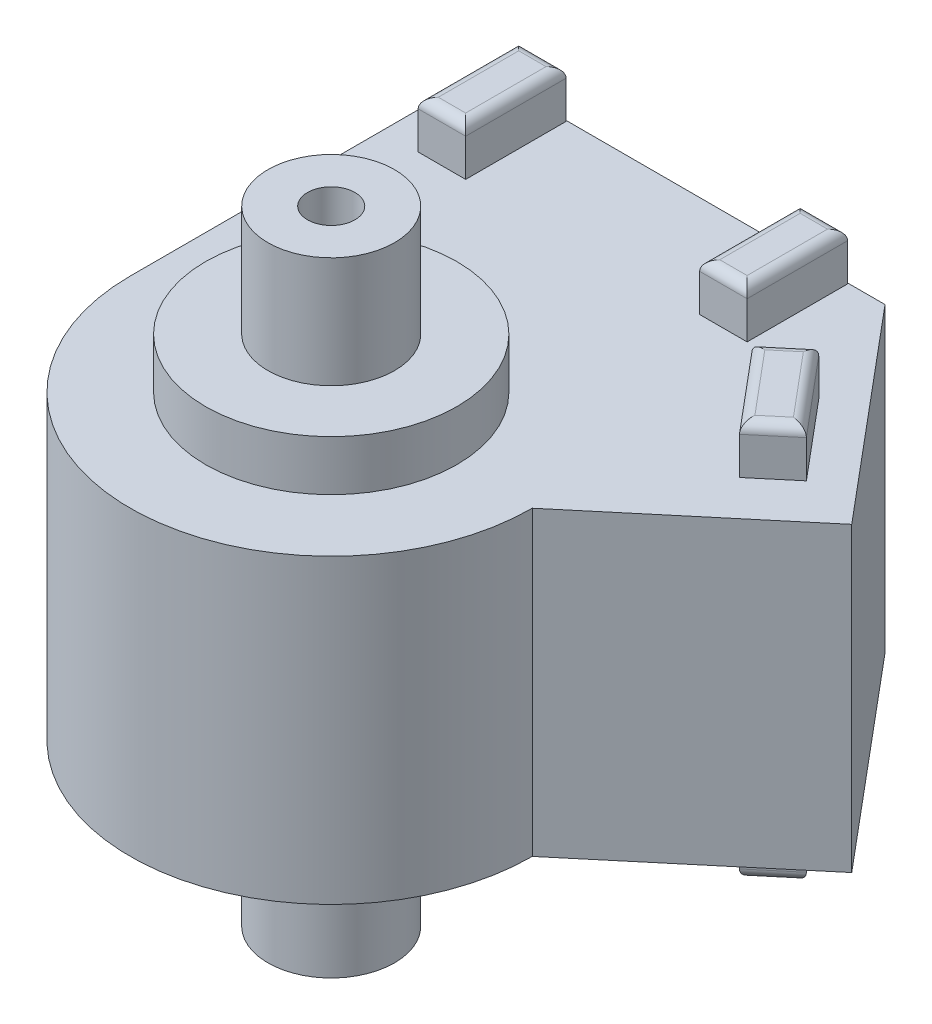
SolidWorks part; units mm, degrees
ref_plane "Front Plane" through (0, 0, 0) normal (0, 0, 1) x (1, 0, 0)
ref_plane "Top Plane" through (0, 0, 0) normal (0, 1, 0) x (1, 0, 0)
ref_plane "Right Plane" through (0, 0, 0) normal (1, 0, 0) x (0, 0, -1)
sketch "Sketch1" plane through (0, 0, 0) normal (0, 0, 1) x (1, 0, 0)
  line L0 (-12.7, -9.525) -> (-12.7, 9.525)
  line L1 (-12.7, 9.525) -> (-7.9375, 9.525)
  line L2 (-7.9375, 9.525) -> (-7.9375, 12.7)
  line L3 (-7.9375, 12.7) -> (-4, 12.7)
  line L4 (-4, 12.7) -> (-4, 19.7)
  line L5 (0, 0) -> (0, 19.7) construction
  line L6 (0, 19.7) -> (-4, 19.7)
  line L7 (0, 0) -> (-12.7, 0) construction
  line L8 (-4, 19.7) -> (4, 19.7) construction
  line L9 (-7.9375, 12.7) -> (7.9375, 12.7) construction
  line L10 (-12.7, 9.525) -> (12.7, 9.525) construction
  line L11 (-12.7, -9.525) -> (-7.9375, -9.525)
  line L12 (-7.9375, -9.525) -> (-7.9375, -12.7)
  line L13 (-7.9375, -12.7) -> (-4, -12.7)
  line L14 (-4, -12.7) -> (-4, -19.7)
  line L15 (-4, -19.7) -> (0, -19.7)
  line L16 (0, -19.7) -> (0, 19.7)
  point P9 (0, 9.525)
  point P12 (0, 19.7)
  point P14 (0, 12.7)
  dimension "D1" = 19.05
  dimension "D2" = 3.175
  dimension "D3" = 7
  dimension "D4" = 8
  dimension "D5" = 15.875
  dimension "D6" = 25.4
  dimension "D7" = 25.4
revolve "Revolve1" add sketch "Sketch1" angle 360 about L5 region at (-5.3061, 0, 0)
sketch "Sketch2" plane through (0, 9.525, 0) normal (0, 1, 0) x (1, 0, 0)
  line L0 (12.7, 0) -> (23.6726, 9.2071)
  line L1 (23.6726, 9.2071) -> (12.7, 22.2837)
  line L3 (12.7, 22.2837) -> (-12.7, 22.2837)
  line L4 (-12.7, 22.2837) -> (-12.7, 0)
  line L5 (-12.7, 0) -> (12.7, 0)
  line L6 (12.7, 0) -> (12.7, 22.2837) construction
  circle A0 centre (0, 0) radius 12.7 construction
  dimension "D1" = 50
  dimension "D2" = 25.4
extrude "Boss-Extrude1" add sketch "Sketch2" against normal up to surface (19.05 mm away) up to face at (7.9375, -9.525, 0)
sketch "Sketch3" plane through (0, 19.7, 0) normal (0, 1, 0) x (1, 0, 0)
  circle A0 centre (0, 0) radius 1.4986
  dimension "D1" = 2.9972
extrude "Cut-Extrude1" cut sketch "Sketch3" against normal through all
sketch "Sketch4" plane through (0, 9.525, 0) normal (0, 1, 0) x (1, 0, 0)
  line L5 (15.7794, 15.0179) -> (13.4834, 13.0913)
  line L6 (13.4834, 13.0913) -> (17.5651, 8.227)
  line L7 (17.5651, 8.227) -> (19.8611, 10.1535)
  line L8 (19.8611, 10.1535) -> (15.7794, 15.0179)
  line L9 (12.7, 0) -> (23.6726, 9.2071) construction
  line L10 (23.6726, 9.2071) -> (12.7, 22.2837) construction
  dimension "D1" = 2.9972
  dimension "D2" = 6.35
  dimension "D3" = 3.175
  dimension "D4" = 2.3114
extrude "Boss-Extrude2" add sketch "Sketch4" along normal blind 2.9972
sketch "Sketch5" plane through (0, 9.525, 0) normal (0, 1, 0) x (1, 0, 0)
  line L0 (-12.7, 22.2837) -> (-12.7, 0) construction
  line L1 (-10.3886, 22.2329) -> (-7.3914, 22.2329)
  line L2 (-10.3886, 22.2329) -> (-10.3886, 15.8829)
  line L3 (-10.3886, 15.8829) -> (-7.3914, 15.8829)
  line L4 (-7.3914, 22.2329) -> (-7.3914, 15.8829)
  line L5 (-10.3886, 22.2329) -> (-7.3914, 15.8829) construction
  line L6 (-10.3886, 15.8829) -> (-7.3914, 22.2329) construction
  line L7 (7.3914, 22.2329) -> (10.3886, 22.2329)
  line L8 (7.3914, 22.2329) -> (7.3914, 15.8829)
  line L9 (7.3914, 15.8829) -> (10.3886, 15.8829)
  line L10 (10.3886, 22.2329) -> (10.3886, 15.8829)
  line L11 (7.3914, 22.2329) -> (10.3886, 15.8829) construction
  line L12 (7.3914, 15.8829) -> (10.3886, 22.2329) construction
  line L13 (12.7, 22.2837) -> (-12.7, 22.2837) construction
  point P0 (-8.89, 19.0579)
  point P5 (8.89, 19.0579)
  dimension "D1" = 2.9972
  dimension "D2" = 2.9972
  dimension "D3" = 6.35
  dimension "D4" = 2.3114
  dimension "D5" = 17.78
  dimension "D6" = 0.0508
extrude "Boss-Extrude3" add sketch "Sketch5" along normal blind 2.9972
fillet "Fillet1" radius 0.635 12 edges at (18.7131, 12.5222, -9.1902) (15.5242, 12.5222, -10.6591) (14.6314, 12.5222, -14.0546) (17.8202, 12.5222, -12.5857) (8.89, 12.5222, -15.8829) (7.3914, 12.5222, -19.0579) (8.89, 12.5222, -22.2329) (10.3886, 12.5222, -19.0579) (-8.89, 12.5222, -15.8829) (-10.3886, 12.5222, -19.0579) (-8.89, 12.5222, -22.2329) (-7.3914, 12.5222, -19.0579)
ref_plane "Plane1" through (0, 0, 0) normal (0, 1, 0) x (1, 0, 0)
mirror "Mirror1" about plane through (0, 0, 0) normal (0, 1, 0) of "Fillet1", "Boss-Extrude3", "Boss-Extrude2"
